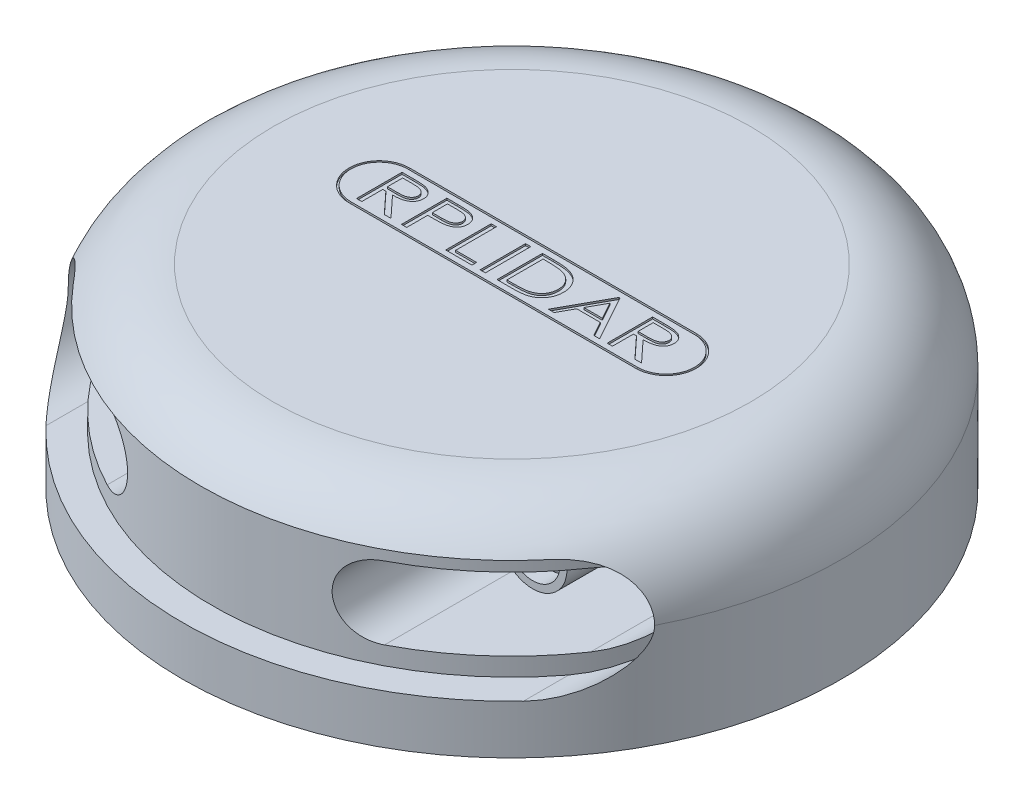
SolidWorks part; units mm, degrees
ref_plane "Ön Düzlem" through (0, 0, 0) normal (0, 0, 1) x (1, 0, 0)
ref_plane "Üst Düzlem" through (0, 0, 0) normal (0, 1, 0) x (1, 0, 0)
ref_plane "Sağ Düzlem" through (0, 0, 0) normal (1, 0, 0) x (0, 0, -1)
sketch "Çizim1" plane through (0, 0, 0) normal (0, 1, 0) x (1, 0, 0)
  circle A0 centre (0, 0) radius 36.25
  dimension "D1" = 72.5
extrude "Yükseklik-Ekstrüzyon1" add sketch "Çizim1" along normal blind 21.4
fillet "Radyus1" radius 10 1 edges at (0, 21.4, 36.25)
sketch "Çizim2" plane through (0, 0, 0) normal (0, 0, 1) x (1, 0, 0)
  line L0 (-36.25, 11.4) -> (36.25, 11.4) construction
  line L1 (-26.25, 11.4) -> (26.25, 11.4) construction
  line L2 (-26.25, 17.4) -> (26.25, 17.4)
  line L3 (-26.25, 5.4) -> (26.25, 5.4)
  arc A0 (-26.25, 17.4) -> (-26.25, 5.4) centre (-26.25, 11.4) ccw
  arc A1 (26.25, 5.4) -> (26.25, 17.4) centre (26.25, 11.4) ccw
  point P6 (0, 11.4)
  dimension "D1" = 10
  dimension "D2" = 10
  dimension "D3" = 12
extrude "Kes-Ekstrüzyon1" cut sketch "Çizim2" along normal blind 41.4 contours L3 A1 L2 A0
sketch "Çizim3" plane through (0, 5.4, 0) normal (0, 1, 0) x (1, 0, 0)
  circle A0 centre (0, 0) radius 33.0032
extrude "Yükseklik-Ekstrüzyon2" add sketch "Çizim3" along normal blind 12.4
sketch "Çizim4" plane through (0, 0, 0) normal (0, 0, 1) x (1, 0, 0)
  line L0 (-32.25, 11.4) -> (32.25, 11.4) construction
  line L1 (-27.25, 11.4) -> (-15.25, 11.4) construction
  line L2 (-27.25, 15.4) -> (-15.25, 15.4)
  line L3 (-27.25, 7.4) -> (-15.25, 7.4)
  line L4 (0, 0) -> (0, 17.4) construction
  line L5 (-26.25, 17.4) -> (26.25, 17.4) construction
  line L6 (27.25, 11.4) -> (15.25, 11.4) construction
  line L7 (27.25, 15.4) -> (15.25, 15.4)
  line L8 (27.25, 7.4) -> (15.25, 7.4)
  arc A0 (-27.25, 15.4) -> (-27.25, 7.4) centre (-27.25, 11.4) ccw
  arc A1 (-15.25, 7.4) -> (-15.25, 15.4) centre (-15.25, 11.4) ccw
  arc A2 (27.25, 15.4) -> (27.25, 7.4) centre (27.25, 11.4) cw
  arc A3 (15.25, 7.4) -> (15.25, 15.4) centre (15.25, 11.4) cw
  point P6 (-21.25, 11.4)
  point P18 (21.25, 11.4)
  dimension "D1" = 8
  dimension "D2" = 5
  dimension "D3" = 12
extrude "Kes-Ekstrüzyon2" cut sketch "Çizim4" along normal blind 44.4
sketch "Çizim5" plane through (0, 0, 0) normal (0, 0, 1) x (1, 0, 0)
  line L0 (-32.25, 11.4) -> (32.25, 11.4) construction
  circle A0 centre (18.2814, 11.4) radius 3.775
  circle A1 centre (18.2814, 11.4) radius 3
  circle A2 centre (-26.25, 11.4) radius 3
  circle A3 centre (-26.25, 11.4) radius 1.5
  dimension "D1" = 6
  dimension "D2" = 6
  dimension "D3" = 3
  dimension "D4" = 7.55
extrude "Yükseklik-Ekstrüzyon4" add sketch "Çizim5" along normal blind 16
sketch "Çizim6" plane through (0, 0, 0) normal (0, -1, 0) x (1, 0, 0)
  circle A0 centre (0, 0) radius 35
  dimension "D1" = 70
extrude "Kes-Ekstrüzyon3" cut sketch "Çizim6" against normal blind 5
sketch "Çizim8" plane through (0, 0, 16) normal (0, 0, 1) x (1, 0, 0)
  circle A0 centre (-26.25, 11.4) radius 1.5
  circle A1 centre (18.2814, 11.4) radius 3
extrude "Yükseklik-Ekstrüzyon5" add sketch "Çizim8" along normal blind 1 from offset 3 offset against normal yes
sketch "Çizim9" plane through (0, 21.4, 0) normal (0, 1, 0) x (1, 0, 0)
  text T0 "RPLIDAR" font "Century Gothic" height 5
extrude "Kes-Ekstrüzyon4" cut sketch "Çizim9" against normal blind 0.2
sketch "Çizim10" plane through (0, 21.4, 0) normal (0, 1, 0) x (1, 0, 0)
  line L0 (-14.8113, 0.221) -> (16.7289, 0.221) construction
  line L1 (-14.8113, -2.279) -> (-14.8113, 2.721) construction
  line L2 (-14.8113, 0.221) -> (16.7289, 0.221) construction
  line L3 (-14.8113, 3.3453) -> (16.7289, 3.3453)
  line L4 (-14.8113, -2.9033) -> (16.7289, -2.9033)
  line L5 (-14.8113, 3.5453) -> (16.7289, 3.5453)
  line L6 (-14.8113, -3.1033) -> (16.7289, -3.1033)
  arc A0 (-14.8113, 3.3453) -> (-14.8113, -2.9033) centre (-14.8113, 0.221) ccw
  arc A1 (16.7289, -2.9033) -> (16.7289, 3.3453) centre (16.7289, 0.221) ccw
  arc A2 (16.7289, -3.1033) -> (16.7289, 3.5453) centre (16.7289, 0.221) ccw
  arc A3 (-14.8113, 3.5453) -> (-14.8113, -3.1033) centre (-14.8113, 0.221) ccw
  point P4 (0.9588, 0.221)
  dimension "D1" = 0.2
extrude "Kes-Ekstrüzyon5" cut sketch "Çizim10" against normal blind 0.2
